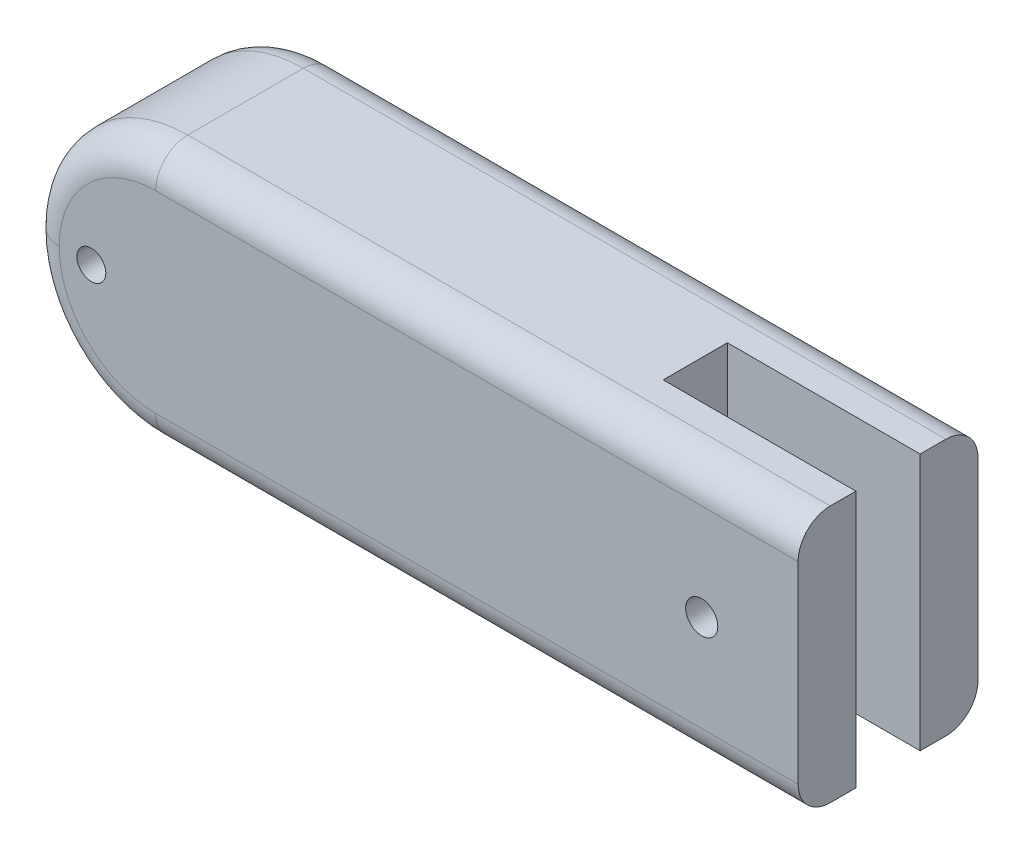
SolidWorks part; units mm, degrees
ref_plane "Plano frontal" through (0, 0, 0) normal (0, 0, 1) x (1, 0, 0)
ref_plane "Plano superior" through (0, 0, 0) normal (0, 1, 0) x (1, 0, 0)
ref_plane "Plano direito" through (0, 0, 0) normal (1, 0, 0) x (0, 0, -1)
sketch "Esboço1" plane through (0, 0, 0) normal (0, 0, 1) x (1, 0, 0)
  line L0 (0, 20) -> (120, 20) construction
  line L1 (0, 0) -> (120, 0)
  line L2 (0, 0) -> (0, 40)
  line L3 (0, 40) -> (120, 40)
  line L4 (120, 0) -> (120, 40)
  circle A0 centre (10, 20) radius 2.25
  dimension "D3" = 4.5
  dimension "D6" = 10
  dimension "D1" = 40
  dimension "D2" = 120
extrude "Ressalto-extrusão1" add sketch "Esboço1" along normal blind 28
sketch "Esboço2" plane through (120, 0, 0) normal (1, 0, 0) x (0, 0, -1)
  line L0 (-14, 40) -> (-14, 0) construction
  line L1 (-28, 40) -> (0, 40) construction
  line L2 (-28, 0) -> (0, 0) construction
  line L4 (-19, 0) -> (-9, 0)
  line L5 (-19, 0) -> (-19, 40)
  line L6 (-19, 40) -> (-9, 40)
  line L7 (-9, 0) -> (-9, 40)
  line L8 (-19, 0) -> (-9, 40) construction
  line L9 (-19, 40) -> (-9, 0) construction
  point P6 (-14, 20)
  dimension "D1" = 10
extrude "Corte-extrusão1" cut sketch "Esboço2" against normal blind 30
fillet "Filete1" radius 20 2 edges at (0, 0, 14) (0, 40, 14)
fillet "Filete2" radius 5 8 edges at (70, 40, 28) (5.8579, 34.1421, 28) (5.8579, 5.8579, 28) (70, 0, 0) (5.8579, 5.8579, 0) (5.8579, 34.1421, 0) (70, 0, 28) (70, 40, 0)
sketch "Esboço3" plane through (0, 0, 28) normal (0, 0, 1) x (1, 0, 0)
  line L0 (120, 5) -> (120, 35) construction
  circle A0 centre (105, 20) radius 2.5
  point P5 (120, 20)
  dimension "D1" = 5
  dimension "D2" = 15
extrude "Corte-extrusão2" cut sketch "Esboço3" against normal blind 40
